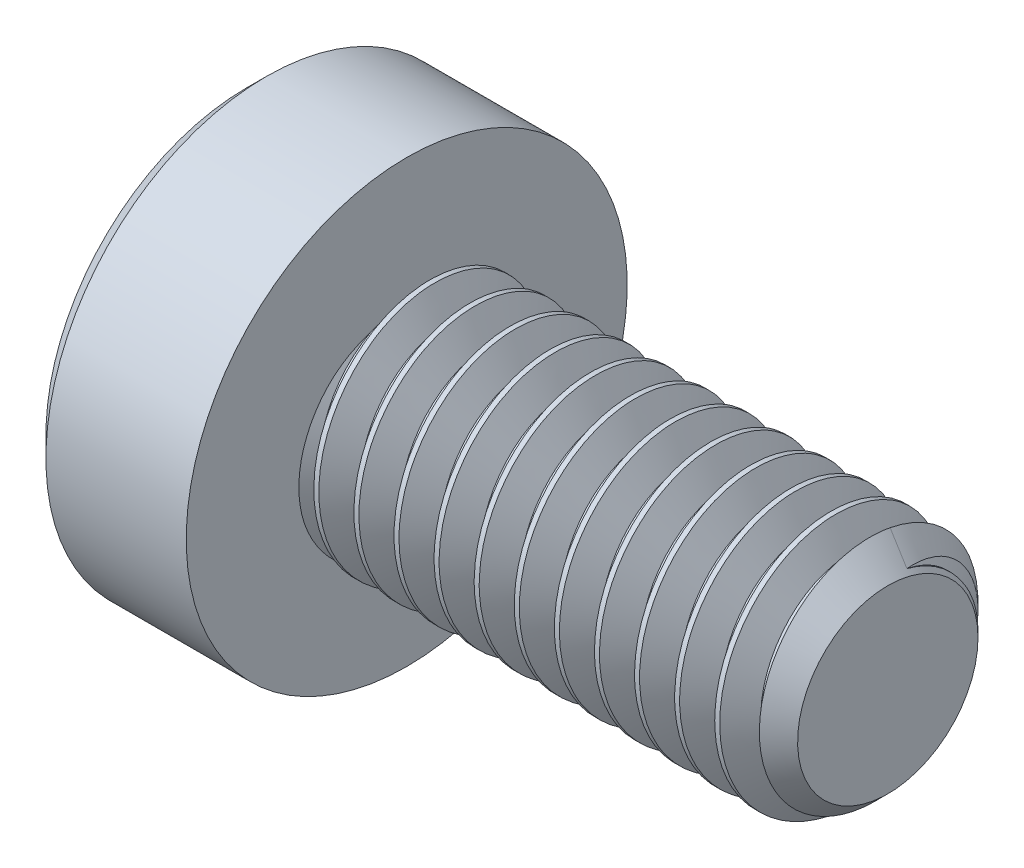
SolidWorks part; units mm, degrees
ref_plane "Front Plane" through (0, 0, 0) normal (0, 0, 1) x (1, 0, 0)
ref_plane "Top Plane" through (0, 0, 0) normal (0, 1, 0) x (1, 0, 0)
ref_plane "Right Plane" through (0, 0, 0) normal (1, 0, 0) x (0, 0, -1)
sketch "Sketch1" plane through (0, 0, 0) normal (0, 0, 1) x (1, 0, 0)
  line L0 (3, 0) -> (-3, 0) construction
  line L1 (3, 1.5) -> (3, -1.5) construction
  line L2 (-3, 2.75) -> (-3, -2.75) construction
  line L3 (-3, 2.75) -> (-4.75, 2.75) construction
  line L4 (-4.75, 2.75) -> (-5, 2.5) construction
  line L5 (-5, 2.5) -> (-5, -2.5) construction
  line L6 (-5, -2.5) -> (-4.75, -2.75) construction
  line L7 (-4.75, -2.75) -> (-3, -2.75) construction
  point P7 (-3.38, 0)
  point P12 (1, -1.5)
  dimension "D1" = 45
  dimension "D2" = 2
  dimension "Dec." = 3
  dimension "Length" = 6
  dimension "Head Dia" = 5.5
  dimension "Head Height" = 2
  dimension "Hex Depth" = 1.62
  dimension "Chamfer" = 0.25
ref_plane "Plane1" through (3, 0, 0) normal (1, 0, 0) x (0, 0, -1)
ref_plane "Plane2" through (-5, 0, 0) normal (1, 0, 0) x (0, 0, -1)
sketch "Sketch2" plane through (3, 0, 0) normal (1, 0, 0) x (0, 0, -1)
  circle A0 centre (0, 0) radius 1.5
extrude "Boss-Extrude1" add sketch "Sketch2" against normal up to vertex (6 mm away) up to point (-3, 0, 0)
sketch "Sketch3" plane through (3, 0, 0) normal (1, 0, 0) x (0, 0, -1)
  circle A0 centre (0, 0) radius 1.5 construction
  circle A1 centre (0, 0) radius 1.5
curve "Helix/Spiral1" pitch 0.5 height 6.5 radius 1.5 centre (3, 0, 0) axis (-1, 0, 0) start towards (0, 1, 0) parameters "Pitch"=0.5
chamfer "Chamfer1" distance 0.375 angle 45 1 edges at (3, 0, -1.5)
sketch "Sketch5" plane through (0, 0, 0) normal (0, 0, 1) x (1, 0, 0)
  line L0 (2.7813, 1.5) -> (3.2187, 1.5)
  line L1 (3.2187, 1.5) -> (3.0313, 1.1752)
  line L2 (3.0313, 1.1752) -> (2.9688, 1.1752)
  line L3 (2.9688, 1.1752) -> (2.7813, 1.5)
  line L4 (3, 1.1752) -> (3, 1.5) construction
  line L5 (2.875, 1.3376) -> (3.125, 1.3376) construction
  dimension "D1" = 60
  dimension "D2" = 0.25
  dimension "D3" = 0.0625
sweep "Cut-Sweep1" cut profiles "Sketch5" path "Helix/Spiral1"
sketch "Sketch4" plane through (-5, 0, 0) normal (1, 0, 0) x (0, 0, -1)
  line L0 (-2.75, 0.7937) -> (2.75, 0.7937) construction
  line L1 (0, 1.1547) -> (-1, 0.5774)
  line L2 (-1, 0.5774) -> (-1, -0.5774)
  line L3 (-1, -0.5774) -> (0, -1.1547)
  line L4 (0, -1.1547) -> (1, -0.5774)
  line L5 (1, -0.5774) -> (1, 0.5774)
  line L6 (1, 0.5774) -> (0, 1.1547)
  line L7 (0, 0) -> (0, 0.7937) construction
  circle A0 centre (0, 0) radius 1 construction
  dimension "D1" = 5.5
  dimension "Hex Size" = 2
  dimension "D2" = 0.7937
sketch "Sketch6" plane through (0, 0, 0) normal (0, 0, 1) x (1, 0, 0)
  line L0 (-4.75, 2.75) -> (-5, 2.5) construction
  line L1 (-3, 2.75) -> (-4.75, 2.75) construction
  line L2 (-3, 2.75) -> (-3, -2.75) construction
  line L3 (-5, 2.5) -> (-5, -2.5) construction
  line L4 (-4.75, 2.75) -> (-5, 2.5)
  line L5 (-3, 2.75) -> (-4.75, 2.75)
  line L6 (-3, 2.75) -> (-3, 0)
  line L7 (-5, 2.5) -> (-5, 0)
  line L8 (-3, 0) -> (-5, 0) construction
  line L9 (-3, 0) -> (-5, 0)
revolve "Revolve1" add sketch "Sketch6" angle 360 about L8
extrude "Cut-Extrude1" cut sketch "Sketch4" along normal up to vertex (1.62 mm away) up to point (-3.38, 0, 0)
sketch "Sketch8" plane through (-5, 0, 0) normal (-1, 0, 0) x (0, 0, 1)
  circle A1 centre (0, 0) radius 1.1547
extrude "Cut-Extrude2" cut sketch "Sketch8" against normal through all draft 45
equation "\"D3@Helix/Spiral1\" = \"Length@Sketch1\"+\"Pitch@Helix/Spiral1\""
equation "\"D3@Sketch5\" = \"Pitch@Helix/Spiral1\"*.125"
equation "\"D2@Sketch5\" = \"Pitch@Helix/Spiral1\"*.50"
equation "\"D1@Chamfer1\" = \"Pitch@Helix/Spiral1\"*.75"
equation "\"D2@Sketch1\" = \"Pitch@Helix/Spiral1\"*4"
equation "\"D1@Sketch4\" = \"Head Dia@Sketch1\""
equation "\"Chamfer@Sketch1\" = \"Head Height@Sketch1\"/8"
